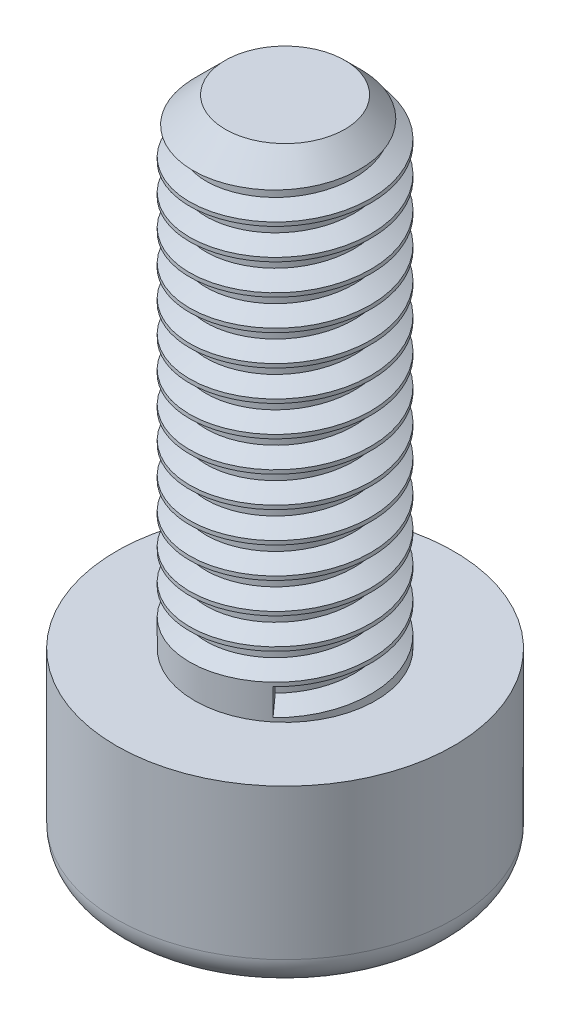
SolidWorks part; units mm, degrees
ref_plane "Front Plane" through (0, 0, 0) normal (0, 0, 1) x (1, 0, 0)
ref_plane "Top Plane" through (0, 0, 0) normal (0, 1, 0) x (1, 0, 0)
ref_plane "Right Plane" through (0, 0, 0) normal (1, 0, 0) x (0, 0, -1)
sketch "Sketch1" plane through (0, 0, 0) normal (0, 1, 0) x (1, 0, 0)
  circle A0 centre (0, 0) radius 2.75
  dimension "D1" = 5.5
extrude "Boss-Extrude1" add sketch "Sketch1" along normal blind 2.95
sketch "Sketch2" plane through (0, 2.95, 0) normal (0, 1, 0) x (1, 0, 0)
  circle A0 centre (0, 0) radius 1.475
  dimension "D1" = 2.95
extrude "Boss-Extrude2" add sketch "Sketch2" along normal blind 7.82
sketch "Sketch3" plane through (0, 0, 0) normal (0, -1, 0) x (1, 0, 0)
  line L1 (0, -1.4434) -> (1.25, -0.7217)
  line L2 (1.25, -0.7217) -> (1.25, 0.7217)
  line L3 (1.25, 0.7217) -> (0, 1.4434)
  line L4 (0, 1.4434) -> (-1.25, 0.7217)
  line L5 (-1.25, 0.7217) -> (-1.25, -0.7217)
  line L6 (-1.25, -0.7217) -> (0, -1.4434)
  circle A0 centre (0, 0) radius 1.25 construction
  dimension "D1" = 2.5
extrude "Cut-Extrude1" cut sketch "Sketch3" against normal blind 1.77
fillet "Fillet1" radius 0.5 1 edges at (0, 0, 2.75)
chamfer "Chamfer1" distance 0.5 angle 45 1 edges at (0, 10.77, 1.475)
thread "Thread1" pitch 0.5 start angle 0, offset 0.5, length 0, pitch 0.5, diameter 2.95
ref_plane "Plane1" through (-1.475, 10.77, 0) normal (0, 0, 1) x (-1, 0, 0)
sketch "Thread Profile1" plane through (-1.475, 10.77, 0) normal (0, 0, 1) x (-1, 0, 0)
  line L0 (0, 0) -> (0, 0.5) construction
  line L11 (0, 0) -> (0, 0.4375)
  line L12 (0, 0.4375) -> (-0.2706, 0.2812)
  line L13 (-0.2706, 0.2812) -> (-0.2706, 0.1562)
  line L15 (-0.2706, 0.1562) -> (0, 0)
  line L17 (-0.2706, 0.2187) -> (0, 0.2187) construction
  point P2 (0, 0)
  dimension "Pitch" = 0.5
  dimension "Profile_Angle" = 60
  dimension "Profile_Land" = 0.125
  dimension "Profile_Height" = 0.2706
